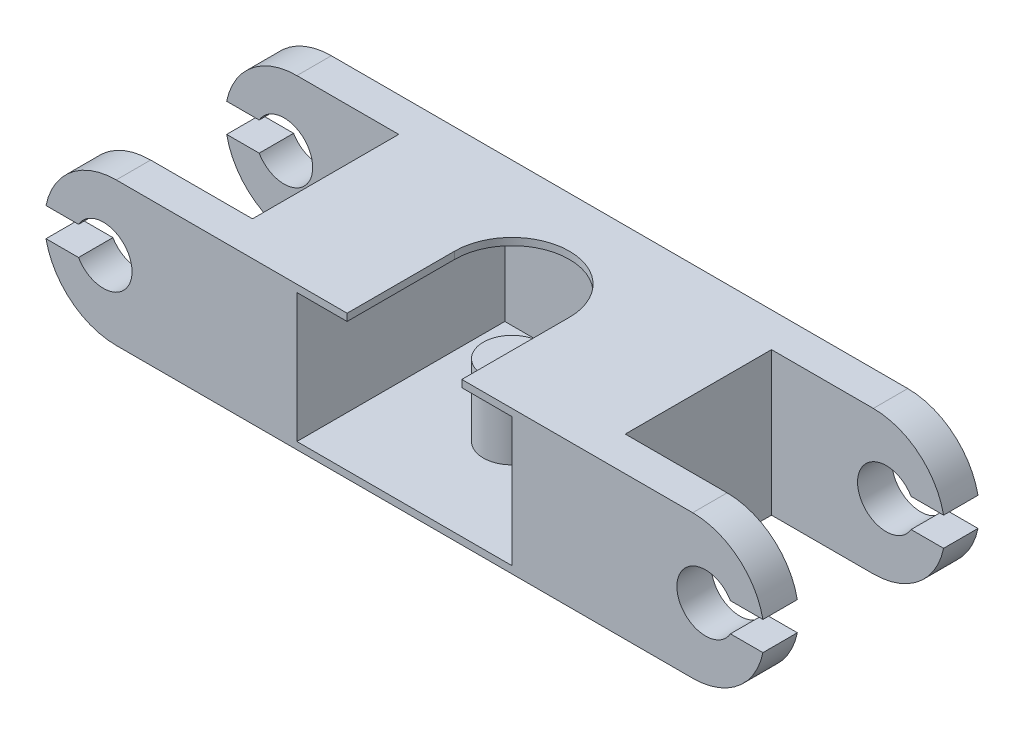
SolidWorks part; units mm, degrees
ref_plane "前视基准面" through (0, 0, 0) normal (0, 0, 1) x (1, 0, 0)
ref_plane "上视基准面" through (0, 0, 0) normal (0, 1, 0) x (1, 0, 0)
ref_plane "右视基准面" through (0, 0, 0) normal (1, 0, 0) x (0, 0, -1)
sketch "草图1" plane through (0, 0, 0) normal (0, 0, 1) x (1, 0, 0)
  line L1 (-25, -5) -> (25, -5)
  line L2 (-25, -5) -> (-25, 5)
  line L3 (-25, 5) -> (25, 5)
  line L4 (25, -5) -> (25, 5)
  line L5 (-25, -5) -> (25, 5) construction
  line L6 (-25, 5) -> (25, -5) construction
  point P0 (0, 0)
  dimension "D1" = 50
  dimension "D2" = 10
extrude "凸台-拉伸1" add sketch "草图1" along normal mid plane 15
sketch "草图3" plane through (0, 5, 0) normal (0, 1, 0) x (1, 0, 0)
  line L0 (-4, 0) -> (-4, -11.4989)
  line L1 (-4, -11.4989) -> (4, -11.4989)
  line L2 (4, -11.4989) -> (4, 0)
  line L3 (25, 7.5) -> (-25, 7.5) construction
  arc A0 (4, 0) -> (-4, 0) centre (0, 0) ccw
  point P1 (0, -11.4989)
  point P8 (0, 7.5)
  dimension "D1" = 7.5
  dimension "D2" = 8
extrude "切除-拉伸1" cut sketch "草图3" against normal blind 6
sketch "草图4" plane through (0, 0, 7.5) normal (0, 0, 1) x (1, 0, 0)
  line L0 (25, 5) -> (4, 5) construction
  line L1 (-7.5, -4.5) -> (7.5, -4.5)
  line L2 (-7.5, -4.5) -> (-7.5, 4.5)
  line L3 (-7.5, 4.5) -> (7.5, 4.5)
  line L4 (7.5, -4.5) -> (7.5, 4.5)
  line L5 (-7.5, -4.5) -> (7.5, 4.5) construction
  line L6 (-7.5, 4.5) -> (7.5, -4.5) construction
  point P0 (0, 0)
  dimension "D1" = 0.5
  dimension "D2" = 15
extrude "切除-拉伸2" cut sketch "草图4" against normal blind 14.5
sketch "草图5" plane through (0, -4.5, 0) normal (0, 1, 0) x (1, 0, 0)
  circle A0 centre (0, 0) radius 2
  dimension "D1" = 4
extrude "凸台-拉伸2" add sketch "草图5" along normal blind 5
sketch "草图6" plane through (0, 5, 0) normal (0, 1, 0) x (1, 0, 0)
  line L0 (-25, -7.5) -> (-25, 7.5) construction
  line L1 (-25, 5.1) -> (-13, 5.1)
  line L2 (-25, 5.1) -> (-25, -5.1)
  line L3 (-25, -5.1) -> (-13, -5.1)
  line L4 (-13, 5.1) -> (-13, -5.1)
  line L5 (0, 0) -> (0, 10.6174) construction
  line L6 (13, 5.1) -> (13, -5.1)
  line L7 (25, -5.1) -> (13, -5.1)
  line L8 (25, 5.1) -> (25, -5.1)
  line L9 (25, 5.1) -> (13, 5.1)
  point P9 (-13, 0)
  dimension "D1" = 10.2
  dimension "D2" = 12
extrude "切除-拉伸3" cut sketch "草图6" against normal through all
sketch "草图7" plane through (0, 0, 7.5) normal (0, 0, 1) x (1, 0, 0)
  line L0 (-25, 5) -> (-25, -5) construction
  line L1 (-25, 1) -> (-22.7321, 1)
  line L2 (-25, 1) -> (-25, -1)
  line L3 (-25, -1) -> (-22.7321, -1)
  line L4 (-4, 5) -> (-25, 5) construction
  line L5 (0, 6.6536) -> (0, -6.6536) construction
  line L6 (25, -1) -> (22.7321, -1)
  line L7 (25, 1) -> (25, -1)
  line L8 (25, 1) -> (22.7321, 1)
  arc A0 (-22.7321, -1) -> (-22.7321, 1) centre (-21, 0) ccw
  arc A1 (22.7321, -1) -> (22.7321, 1) centre (21, 0) cw
  point P6 (-25, 0)
  point P14 (0, 0)
  dimension "D1" = 4
  dimension "D2" = 4
  dimension "D3" = 5
  dimension "D4" = 2
extrude "切除-拉伸4" cut sketch "草图7" against normal through all both and the other way through all
fillet "圆角1" radius 5 8 edges at (25, 5, -6.3) (25, 5, 6.3) (25, -5, -6.3) (25, -5, 6.3) (-25, -5, -6.3) (-25, 5, -6.3) (-25, 5, 6.3) (-25, -5, 6.3)
sketch "草图8" plane through (0, 0, 7.5) normal (0, 0, 1) x (1, 0, 0)
  line L0 (-20.101, -5) -> (20.101, -5) construction
  line L1 (0, 0) -> (0, -3) construction
  circle A0 centre (10, -3) radius 0.75
  circle A1 centre (-10, -3) radius 0.75
  dimension "D1" = 1.5
  dimension "D2" = 2
  dimension "D3" = 10
extrude "切除-拉伸5" cut sketch "草图8" against normal blind 10 from offset 5 offset against normal yes
extrude "填料-伸長1" add sketch "草图5<2>" against normal blind 0.5
sketch "草图5<2>" plane through (0, -4.5, 0) normal (0, 1, 0) x (1, 0, 0) same geometry as "草图5"
extrude "除料-伸長1" cut sketch "草图5<3>" against normal blind 10
sketch "草图5<3>" plane through (0, -4.5, 0) normal (0, 1, 0) x (1, 0, 0) same geometry as "草图5"
